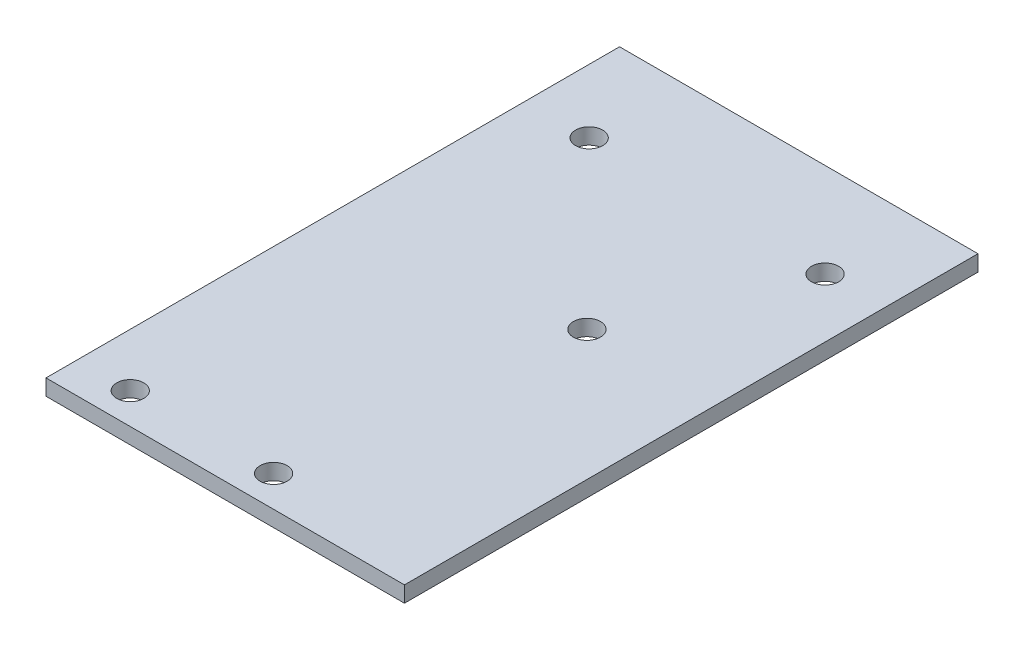
SolidWorks part; units mm, degrees
note: The reader was unsure of these and kept them because the rebuilt part matched: thickness of "Base-Flange1", "Sheet-Metal(1)", "Sheet-Metal(2)".
ref_plane "Front Plane" through (0, 0, 0) normal (0, 0, 1) x (1, 0, 0)
ref_plane "Top Plane" through (0, 0, 0) normal (0, 1, 0) x (1, 0, 0)
ref_plane "Right Plane" through (0, 0, 0) normal (1, 0, 0) x (0, 0, -1)
sketch "Sketch1" plane through (0, 0, 0) normal (0, 1, 0) x (1, 0, 0)
  line L1 (22.5, -36) -> (-22.5, -36)
  line L2 (22.5, -36) -> (22.5, 36)
  line L3 (22.5, 36) -> (-22.5, 36)
  line L4 (-22.5, -36) -> (-22.5, 36)
  point P0 (0, 0)
  dimension "D1" = 72
  dimension "D2" = 45
base flange "Base-Flange1" sketch "Sketch1" thickness 2 reverse thickness direction no parameters "D1"=0.762
sketch "Sketch6" plane through (0, 0, 0) normal (0, 1, 0) x (1, 0, 0)
  line L1 (30, -38) -> (-30, -38)
  line L2 (30, -38) -> (30, 38)
  line L3 (30, 38) -> (-30, 38)
  line L4 (-30, -38) -> (-30, 38)
  line L5 (30, -38) -> (-30, 38) construction
  line L6 (30, 38) -> (-30, -38) construction
  point P0 (0, 0)
  dimension "D1" = 60
  dimension "D2" = 76
sketch "Sketch7" plane through (0, 0, 0) normal (0, 1, 0) x (1, 0, 0)
  line L0 (-22.5, 8) -> (22.5, 8)
  line L1 (-22.5, 36) -> (-22.5, -36) construction
  line L2 (22.5, -36) -> (22.5, 36) construction
  line L3 (30, 38) -> (-30, 38) construction
  dimension "D1" = 30
sketch "Sketch8" plane through (0, -2, 0) normal (0, -1, 0) x (-1, 0, 0)
  line L0 (-22.5, -38) -> (22.5, -38)
  line L1 (-22.5, -36) -> (-22.5, 36) construction
  line L2 (22.5, 36) -> (22.5, -36) construction
  line L3 (-30, -38) -> (30, -38) construction
  line L4 (30, -20.6783) -> (30, 5.81)
  line L5 (30, -38) -> (30, 38) construction
  dimension "D1" = 0
  dimension "D2" = 0
hole_wizard "Need to Reposition" positions "Sketch13" profile "Sketch12" hole size "M3" standard "ANSI Metric"
sketch "Sketch13" plane through (0, -2, 0) normal (0, -1, 0) x (-1, 0, 0)
  point P0 (-2.1723, -32.098)
  point P3 (15.8277, -32.098)
  point P6 (-6.1723, 3.23)
  point P9 (-15.1096, 24.1908)
  point P11 (14.5043, 24.1908)
sketch "Sketch12" plane through (2.1723, -2, 32.098) normal (1, 0, 0) x (0, 0, -1)
  line L0 (0, 0) -> (0, 13.0215)
  line L1 (0, 13.0215) -> (1.7, 12)
  line L2 (1.7, 12) -> (1.7, 0)
  line L5 (1.7, 0) -> (0, 0)
  line L10 (0, 13.0215) -> (-1.7, 12) construction
  line L11 (0, -6.35) -> (0, 107.95) construction
  dimension "Hole Dia." = 3.4
  dimension "Hole Depth" = 12
  dimension "Drill Angle" = 118
sketch "Bend-Lines1" [suppressed] plane through (0, 0, 0) normal (0, 1, 0) x (1, 0, 0)
sketch "Bounding-Box1" [suppressed] plane through (0, 0, 0) normal (0, 1, 0) x (1, 0, 0)
sheet metal parameters "Sheet-Metal(1)" thickness 2 parameters "D1"=0.762
flat pattern "Flat-Pattern(1)" [suppressed]
sketch "Bend-Lines2" plane through (0, 0, 0) normal (0, 1, 0) x (1, 0, 0)
sketch "Bounding-Box2" [suppressed] plane through (0, 0, 0) normal (0, 1, 0) x (1, 0, 0)
sheet metal parameters "Sheet-Metal(2)" thickness 2 parameters "D1"=0.762, "D7"=0.86
flat pattern "Flat-Pattern(1)" [suppressed]
sketch "Bend-Lines2" plane through (0, 0, 0) normal (0, 1, 0) x (1, 0, 0)
sketch3d "Bounding-Box2" [suppressed]
  line L0 (-22.5, 36, 0) -> (-22.5, -36, 0) construction
  line L1 (22.5, 36, 0) -> (22.5, -36, 0) construction
  line L2 (-22.5, 36, 0) -> (22.5, 36, 0) construction
  line L3 (-22.5, -36, 0) -> (22.5, -36, 0) construction
sketch "Sketch8-1" [suppressed] plane through (0, -0.86, 0) normal (0, -1, 0) x (-1, 0, 0)
  line L0 (-22.5, -38) -> (22.5, -38)
  line L3 (-30, -38) -> (30, -38) construction
  line L4 (30, -20.6783) -> (30, 5.81)
  line L5 (30, -38) -> (30, 38) construction
  dimension "D1" = 0
  dimension "D2" = 0
